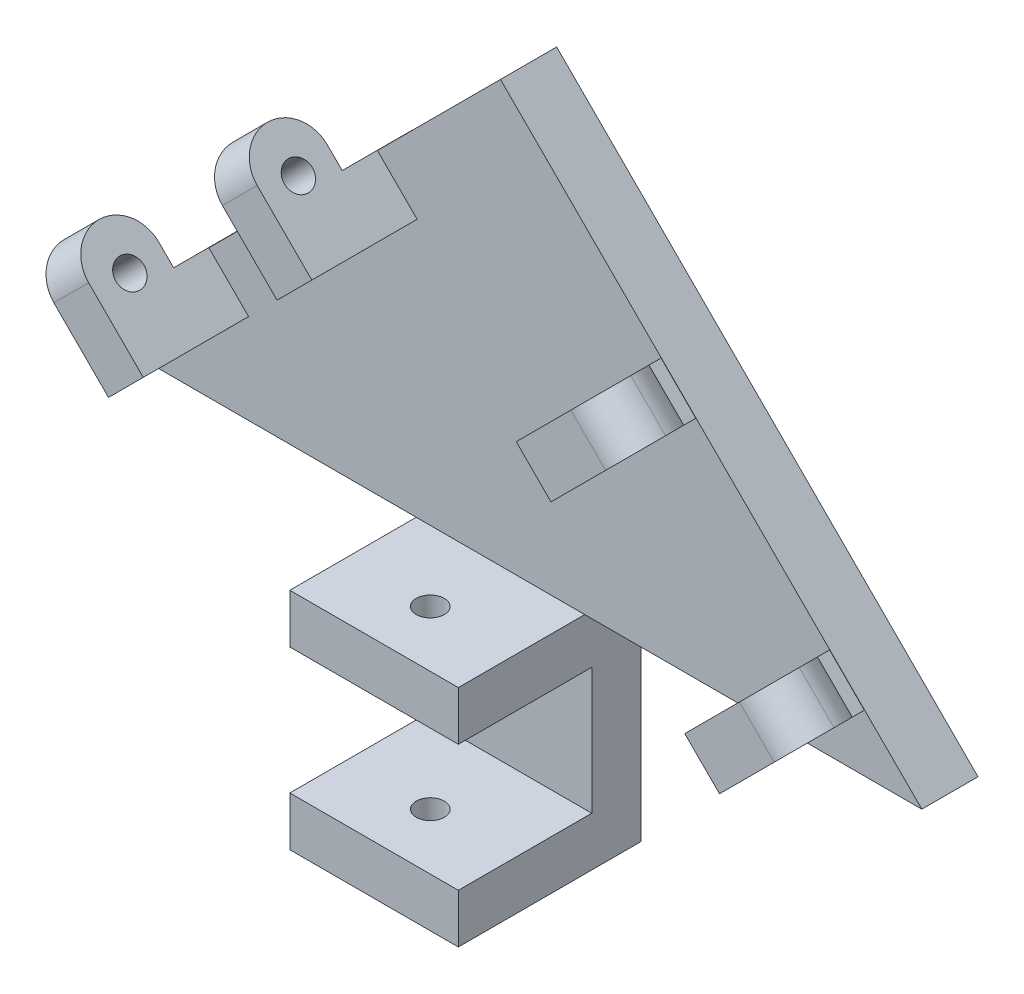
SolidWorks part; units mm, degrees
ref_plane "Front Plane" through (0, 0, 0) normal (0, 0, 1) x (1, 0, 0)
ref_plane "Top Plane" through (0, 0, 0) normal (0, 1, 0) x (1, 0, 0)
ref_plane "Right Plane" through (0, 0, 0) normal (1, 0, 0) x (0, 0, -1)
sketch "Sketch1" plane through (0, 0, 0) normal (0, 0, 1) x (1, 0, 0)
  line L0 (0, 0) -> (30, 0) construction
  line L1 (0, 0) -> (-30, 0) construction
  line L2 (-30, 0) -> (30, 0)
  line L3 (0, 0) -> (0, 35.6261) construction
  line L4 (30, 0) -> (0, 30)
  line L5 (0, 30) -> (-30, 0)
  dimension "D1" = 30
  dimension "D2" = 30
  dimension "D3" = 45
extrude "Boss-Extrude1" add sketch "Sketch1" along normal blind 4
sketch "Sketch2" plane through (0, 0, 4) normal (0, 0, 1) x (1, 0, 0)
  line L0 (0, 30) -> (0, -10) construction
  line L1 (-30, 0) -> (30, 0) construction
  line L2 (-6, 0) -> (6, 0)
  line L3 (-6, 0) -> (-6, -16)
  line L4 (-6, -16) -> (6, -16)
  line L5 (6, 0) -> (6, -16)
  line L6 (-6, 0) -> (6, -16) construction
  line L7 (-6, -16) -> (6, 0) construction
  point P4 (0, -8)
  dimension "D1" = 16
  dimension "D2" = 8
  dimension "D3" = 12
extrude "Boss-Extrude2" add sketch "Sketch2" along normal blind 13 from offset 4 offset against normal yes
sketch "Sketch3" plane through (0, 0, 13) normal (0, 0, 1) x (1, 0, 0)
  line L0 (6, -16) -> (6, 0) construction
  line L1 (-6, -3.5) -> (6, -3.5)
  line L2 (-6, -3.5) -> (-6, -12.5)
  line L3 (-6, -12.5) -> (6, -12.5)
  line L4 (6, -3.5) -> (6, -12.5)
  line L5 (-6, -3.5) -> (6, -12.5) construction
  line L6 (-6, -12.5) -> (6, -3.5) construction
  line L7 (6, 0) -> (30, 0) construction
  point P0 (0, -8)
  dimension "D1" = 9
  dimension "D2" = 8
extrude "Cut-Extrude1" cut sketch "Sketch3" against normal blind 9.5
sketch "Sketch4" plane through (0, -16, 0) normal (0, -1, 0) x (1, 0, 0)
  line L0 (-6, 13) -> (6, 13) construction
  line L1 (6, 13) -> (6, 0) construction
  circle A0 centre (0, 9) radius 1
  dimension "D1" = 4
  dimension "D2" = 6
extrude "Cut-Extrude2" cut sketch "Sketch4" against normal blind 16
sketch "Sketch5" plane through (0, 0, 4) normal (0, 0, 1) x (1, 0, 0)
  line L0 (-10, 20) -> (10, 20) construction
  line L1 (0, 30) -> (-30, 0) construction
  line L2 (30, 0) -> (0, 30) construction
  line L3 (-22, 8) -> (22, 8) construction
  line L4 (-10, 20) -> (-13.5355, 23.5355) construction
  line L5 (-22, 8) -> (-25.5355, 11.5355) construction
  line L6 (12.687, 17.313) -> (16.2225, 20.8485) construction
  line L7 (24.687, 5.313) -> (28.2225, 8.8485) construction
  line L8 (-8.409, 15.9341) -> (-14.0659, 21.591)
  line L9 (-8.409, 15.9341) -> (-5.9341, 18.409)
  line L10 (-14.0659, 21.591) -> (-11.591, 24.0659)
  line L11 (-5.9341, 18.409) -> (-11.591, 24.0659)
  line L12 (-8.409, 15.9341) -> (-11.591, 24.0659) construction
  line L13 (-14.0659, 21.591) -> (-5.9341, 18.409) construction
  line L14 (-20.409, 3.9341) -> (-26.0659, 9.591)
  line L15 (-20.409, 3.9341) -> (-17.9341, 6.409)
  line L16 (-26.0659, 9.591) -> (-23.591, 12.0659)
  line L17 (-17.9341, 6.409) -> (-23.591, 12.0659)
  line L18 (-20.409, 3.9341) -> (-23.591, 12.0659) construction
  line L19 (-26.0659, 9.591) -> (-17.9341, 6.409) construction
  line L20 (22, 8) -> (25.5355, 11.5355) construction
  line L21 (10, 20) -> (13.5355, 23.5355) construction
  line L22 (8.6211, 15.722) -> (14.278, 21.3789)
  line L23 (8.6211, 15.722) -> (11.096, 13.2471)
  line L24 (14.278, 21.3789) -> (16.7529, 18.904)
  line L25 (11.096, 13.2471) -> (16.7529, 18.904)
  line L26 (8.6211, 15.722) -> (16.7529, 18.904) construction
  line L27 (14.278, 21.3789) -> (11.096, 13.2471) construction
  line L28 (20.6211, 3.722) -> (26.278, 9.3789)
  line L29 (20.6211, 3.722) -> (23.096, 1.2471)
  line L30 (26.278, 9.3789) -> (28.7529, 6.904)
  line L31 (23.096, 1.2471) -> (28.7529, 6.904)
  line L32 (-6, 0) -> (6, 0) construction
  line L33 (-30, 0) -> (-6, 0) construction
  line L34 (20.6211, 3.722) -> (28.7529, 6.904) construction
  line L35 (26.278, 9.3789) -> (23.096, 1.2471) construction
  dimension "D1" = 3.5
  dimension "D2" = 90
  dimension "D3" = 8
  dimension "D4" = 3.5
  dimension "D5" = 90
  dimension "D6" = 3.8
  dimension "D7" = 3.8
  dimension "D8" = 3.5
  dimension "D9" = 3.5
  dimension "D10" = 20
  dimension "D11" = 8
  dimension "D12" = 90
  dimension "D13" = 90
  dimension "D14" = 90
  dimension "D15" = 8
  dimension "D16" = 90
extrude "Boss-Extrude3" add sketch "Sketch5" along normal blind 5 from offset 2.5
sketch "Sketch6" plane through (10.9244, -10.9244, 0) normal (0.7071, -0.7071, 0) x (0.7071, 0.7071, 0)
  line L1 (17.2132, 6.5) -> (25.2132, 6.5) construction
  line L2 (21.2132, 4) -> (21.2132, 0) construction
  circle A0 centre (22.0982, 9) radius 1
  dimension "D1" = 2.5
  dimension "D2" = 0.885
sketch "Sketch7" plane through (-8.2374, -8.2374, 0) normal (-0.7071, -0.7071, 0) x (0, 0, 1)
  line L0 (4, 21.2132) -> (0, 21.2132) construction
  line L1 (11.5, 25.2132) -> (11.5, 17.2132) construction
  circle A0 centre (9, 22.0982) radius 1
  dimension "D1" = 0.885
  dimension "D2" = 2.5
sketch "Sketch8" plane through (0, 0, 11.5) normal (0, 0, 1) x (1, 0, 0)
  line L0 (-20.409, 3.9341) -> (-17.9341, 6.409)
  line L1 (-20.409, 3.9341) -> (-23.2472, 6.7723)
  line L2 (-17.9341, 6.409) -> (-20.7723, 9.2472)
  line L3 (-23.2472, 6.7723) -> (-20.7723, 9.2472)
  line L4 (-8.409, 15.9341) -> (-5.9341, 18.409)
  line L5 (-8.409, 15.9341) -> (-11.245, 18.7701)
  line L6 (-5.9341, 18.409) -> (-8.7701, 21.245)
  line L7 (-11.245, 18.7701) -> (-8.7701, 21.245)
  line L8 (8.6211, 15.722) -> (11.096, 13.2471)
  line L9 (8.6211, 15.722) -> (11.4337, 18.5345)
  line L10 (11.096, 13.2471) -> (13.9086, 16.0597)
  line L11 (11.4337, 18.5345) -> (13.9086, 16.0597)
  line L12 (8.6211, 15.722) -> (11.096, 13.2471) construction
  line L14 (23.096, 1.2471) -> (20.6211, 3.722)
  line L15 (23.096, 1.2471) -> (25.9085, 4.0597)
  line L16 (20.6211, 3.722) -> (23.4337, 6.5345)
  line L17 (25.9085, 4.0597) -> (23.4337, 6.5345)
extrude "Boss-Extrude4" add sketch "Sketch8" against normal blind 10
extrude "Cut-Extrude5" cut sketch "Sketch6" against normal blind 25
extrude "Cut-Extrude6" cut sketch "Sketch7" against normal blind 25
fillet "Fillet2" radius 2.5 8 edges at (15.5154, 20.1414, 11.5) (15.5154, 20.1414, 6.5) (27.5154, 8.1414, 6.5) (27.5154, 8.1414, 11.5) (-24.8284, 10.8284, 6.5) (-12.8284, 22.8284, 6.5) (-12.8284, 22.8284, 11.5) (-24.8284, 10.8284, 11.5)
